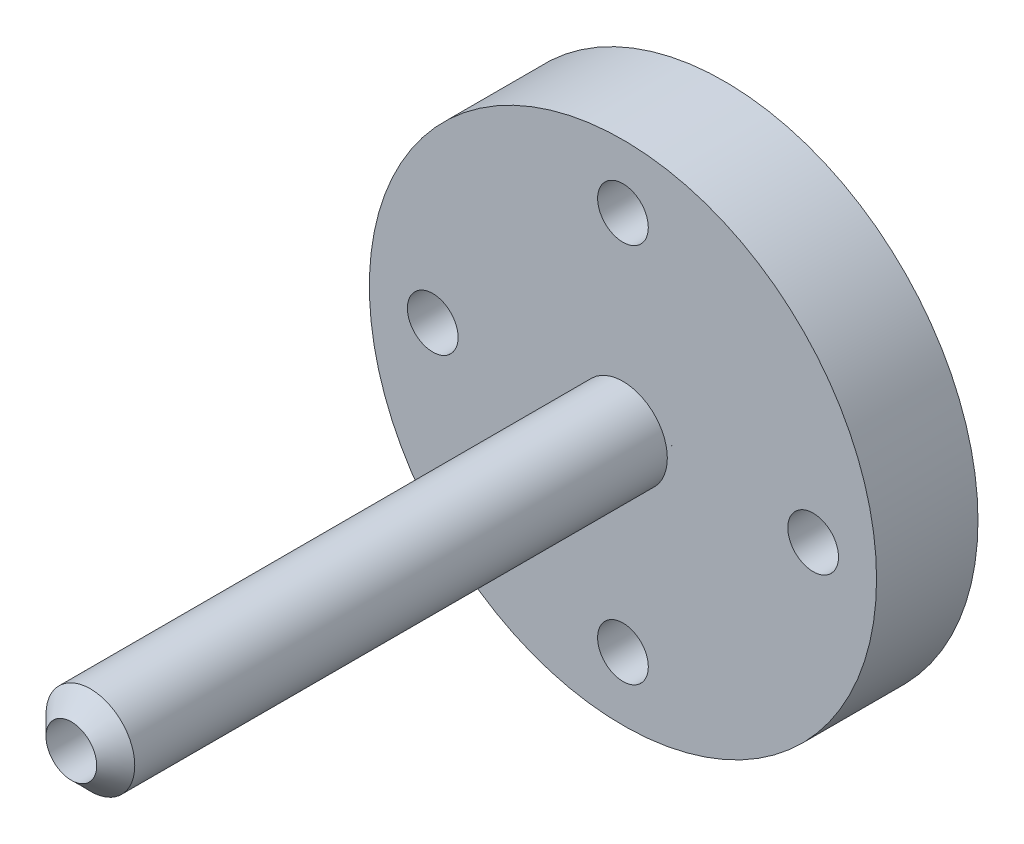
SolidWorks part; units mm, degrees
material "Copper"
ref_plane "Front Plane" through (0, 0, 0) normal (0, 0, 1) x (1, 0, 0)
ref_plane "Top Plane" through (0, 0, 0) normal (0, 1, 0) x (1, 0, 0)
ref_plane "Right Plane" through (0, 0, 0) normal (1, 0, 0) x (0, 0, -1)
sketch "Sketch1" plane through (0, 0, 0) normal (0, 0, 1) x (1, 0, 0)
  circle A0 centre (0, 0) radius 10
  circle A1 centre (0, 0) radius 1
  dimension "D1" = 2
  dimension "D4" = 20
extrude "Boss-Extrude1" add sketch "Sketch1" along normal blind 4
sketch "Sketch2" plane through (0, 0, 4) normal (0, 0, 1) x (1, 0, 0)
  circle A0 centre (0, 0) radius 1 construction
  circle A1 centre (0, 0) radius 1
  circle A2 centre (0, 0) radius 1.75
  dimension "D1" = 3.5
extrude "Boss-Extrude2" add sketch "Sketch2" along normal blind 22
chamfer "Chamfer1" distance 1 angle 45 1 edges at (1.75, 0, 26)
sketch "Sketch3" plane through (0, 0, 4) normal (0, 0, 1) x (1, 0, 0)
  circle A0 centre (0, 0) radius 7.5 construction
  circle A1 centre (0, 7.5) radius 1
  circle A2 centre (-7.5, 0) radius 1
  circle A3 centre (7.5, 0) radius 1
  circle A4 centre (0, -7.5) radius 1
  dimension "D1" = 15
  dimension "D2" = 2
extrude "Cut-Extrude1" cut sketch "Sketch3" against normal through all
sketch "Sketch4" plane through (0, 0, 4) normal (0, 0, 1) x (1, 0, 0)
  circle A0 centre (0, 0) radius 1.75 construction
  circle A1 centre (0, 0) radius 1.75
surface "Surface-Extrude1" sketch "Sketch4"
